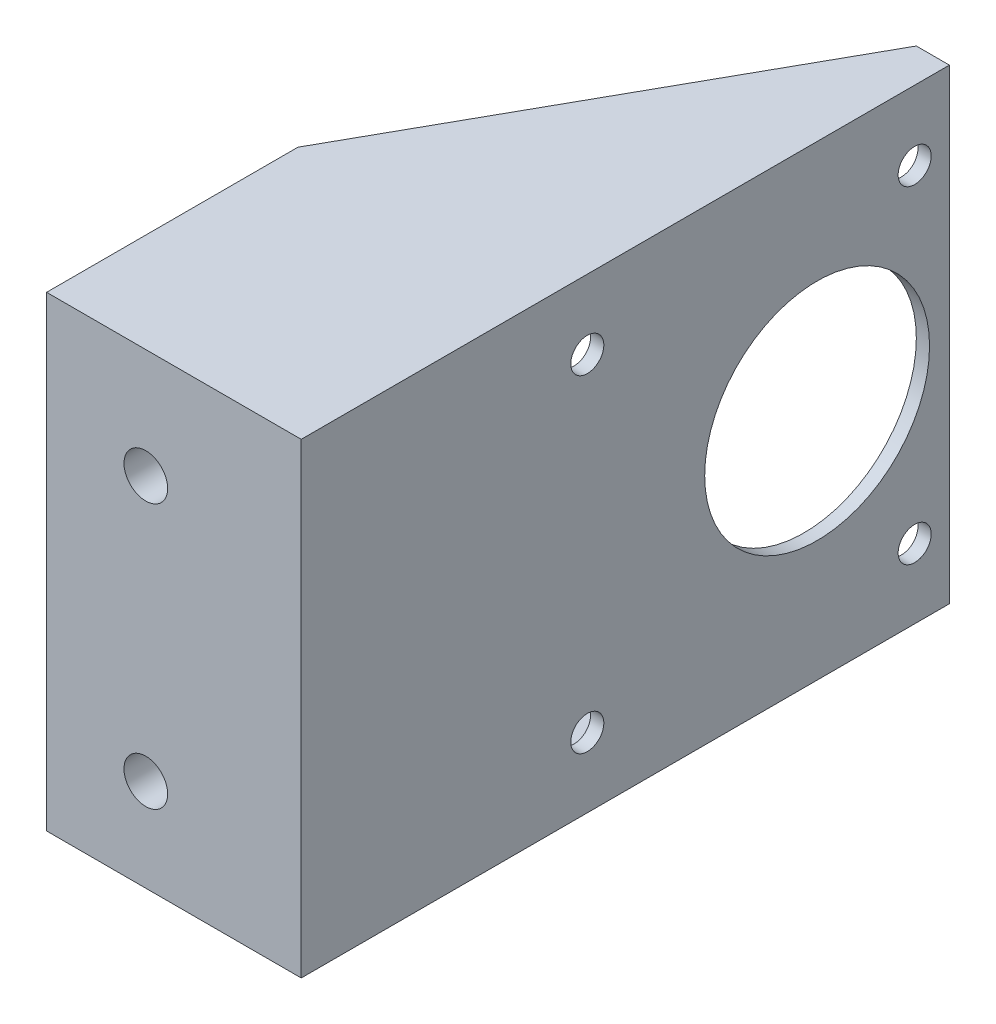
SolidWorks part; units mm, degrees
ref_plane "Front Plane" through (0, 0, 0) normal (1, 0, 0) x (0, 1, 0)
ref_plane "Top Plane" through (0, 0, 0) normal (0, 0, 1) x (0, 1, 0)
ref_plane "Right Plane" through (0, 0, 0) normal (0, 1, 0) x (-1, 0, 0)
sketch "Sketch1" plane through (0, 0, 502.5008) normal (0, 0, -1) x (1, 0, 0)
  line L1 (145.9918, -230.5321) -> (145.9918, 233.4679) construction
  line L2 (145.9918, 35.268) -> (184.4918, 35.268)
  line L3 (145.9918, 35.268) -> (145.9918, -35.268)
  line L4 (145.9918, -35.268) -> (184.4918, -35.268)
  line L5 (184.4918, 35.268) -> (184.4918, -35.268)
  line L7 (145.9918, 30.268) -> (179.9918, 30.268) construction
  line L8 (145.9918, -30.268) -> (182.4918, -30.268) construction
  line L9 (182.4918, -30.268) -> (182.4918, 22.5) construction
  dimension "D1" = 5
  dimension "D2" = 5
  dimension "D3" = 2
extrude "Boss-Extrude1" add sketch "Sketch1" along normal up to surface (38 mm away)
sketch "Sketch3" plane through (0, 35.268, 0) normal (0, 1, 0) x (-1, 0, 0)
  line L6 (-184.4918, 404.5008) -> (-179.4918, 404.5008)
  line L8 (-179.4918, 404.5008) -> (-145.9918, 464.5008)
  line L9 (-145.9918, 464.5008) -> (-184.4918, 464.5008)
  line L10 (-184.4918, 464.5008) -> (-184.4918, 404.5008)
  line L11 (-145.9918, 404.5008) -> (-182.4918, 404.5008) construction
  dimension "D1" = 5
extrude "Boss-Extrude2" add sketch "Sketch3" against normal offset from surface (4 mm away) 1
extrude "Boss-Extrude3" add sketch "Sketch3<2>" along normal offset from surface (4 mm away) 1 from surface starting at face at (165.2418, -35.268, 483.5008)
sketch "Sketch3<2>" plane through (0, 35.268, 0) normal (0, 1, 0) x (-1, 0, 0) same geometry as "Sketch3"
sketch "Sketch4" plane through (184.4918, 0, 0) normal (1, 0, 0) x (0, 1, 0)
  line L0 (-31.268, 404.5008) -> (-35.268, 404.5008) construction
  line L1 (31.268, 464.5008) -> (-31.268, 464.5008)
  line L2 (31.268, 464.5008) -> (31.268, 404.5008)
  line L3 (31.268, 404.5008) -> (-31.268, 404.5008)
  line L4 (-31.268, 464.5008) -> (-31.268, 404.5008)
  line L5 (-31.268, 464.5008) -> (-31.268, 404.5008) construction
  circle A0 centre (-24.75, 409.7508) radius 2.5 construction
  circle A1 centre (24.75, 409.7508) radius 2.5 construction
  circle A2 centre (24.75, 459.2508) radius 2.5 construction
  circle A3 centre (-24.75, 459.2508) radius 2.5 construction
  circle A4 centre (-24.75, 409.7508) radius 2.5
  circle A5 centre (24.75, 409.7508) radius 2.5
  circle A6 centre (24.75, 459.2508) radius 2.5
  circle A7 centre (-24.75, 459.2508) radius 2.5
  circle A8 centre (0, 424.5008) radius 15 construction
  circle A9 centre (0, 424.5008) radius 15
  circle A10 centre (0, 424.5008) radius 17
  line M5 (-31.268, 464.5008) -> (31.268, 464.5008)
  line M6 (31.268, 464.5008) -> (31.268, 404.5008)
  line M12 (-31.268, 404.5008) -> (-31.268, 464.5008)
  dimension "D1" = 2
extrude "Boss-Extrude4" add sketch "Sketch4" against normal up to surface (2 mm away) contours L3 A10 A7 A6 A5 A4 M6 M5 M12 region at (184.4918, 30.4014, 434.5008)
sketch "Sketch5" plane through (0, 0, 464.5008) normal (0, 0, 1) x (1, 0, 0)
  line L0 (156.8668, 230.5321) -> (156.8668, -233.4679) construction
  line L1 (165.1168, 230.5321) -> (165.1168, -233.4679) construction
  line L2 (156.8668, 230.5321) -> (156.8668, -233.4679)
  line L3 (165.1168, 230.5321) -> (165.1168, -233.4679)
  line L4 (160.9918, 25.8381) -> (160.9918, -1.268) construction
  line L5 (165.1168, -1.268) -> (156.8668, -1.268) construction
  line L8 (179.4918, -31.268) -> (145.9918, -31.268) construction
  line L9 (179.4918, -31.268) -> (145.9918, -31.268)
  point P8 (160.9918, -21.268)
  point P9 (160.9918, 18.732)
  dimension "D1" = 40
  dimension "D2" = 30
hole_wizard "CSK for M6 Flat Head Machine Screw1" positions "Sketch5" profile "Sketch6" countersink size "M6" standard "ANSI Metric" end condition through all
sketch "Sketch6" plane through (160.9918, 18.732, 464.5008) normal (1, 0, 0) x (0, 1, 0)
  line L0 (0, 0) -> (0, 38)
  line L1 (0, 38) -> (3.3, 38)
  line L2 (3.3, 38) -> (3.3, 3)
  line L3 (3.3, 3) -> (6.3, 0)
  line L5 (6.3, 0) -> (0, 0)
  line L6 (-3.3, 3) -> (-6.3, 0) construction
  line L11 (0, -6.35) -> (0, 107.95) construction
  dimension "Thru Hole Dia." = 6.6
  dimension "Thru Hole Depth" = 38
  dimension "Near C'Sink Dia." = 12.6
  dimension "Near C'Sink Angle" = 90
